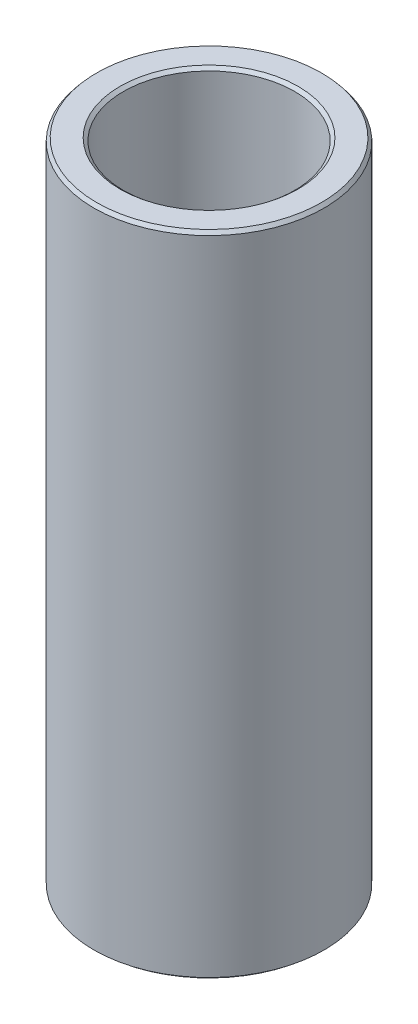
SolidWorks part; units mm, degrees
ref_plane "Front Plane" through (0, 0, 0) normal (0, 0, 1) x (1, 0, 0)
ref_plane "Top Plane" through (0, 0, 0) normal (0, 1, 0) x (1, 0, 0)
ref_plane "Right Plane" through (0, 0, 0) normal (1, 0, 0) x (0, 0, -1)
sketch "Sketch1" plane through (0, 0, 0) normal (0, 1, 0) x (1, 0, 0)
  circle A0 centre (0, 0) radius 30
  dimension "SLEEVE_OD" = 60
extrude "Boss-Extrude1" add sketch "Sketch1" along normal blind 169.0101
sketch "Sketch2" plane through (0, 0, 0) normal (0, 1, 0) x (1, 0, 0)
  circle A0 centre (0, 0) radius 22.3253
  dimension "BORE_D" = 44.6506
extrude "Cut-Extrude1" cut sketch "Sketch2" along normal through all
chamfer "Chamfer1" distance 0.876 angle 39.454 4 edges at (0, 169.0101, 22.3253) (0, 0, 22.3253) (0, 0, 30) (0, 169.0101, 30) first distance on face at (0, 169.0101, 22.3253) first distance on face at (0, 0, 22.3253) first distance on face at (0, 169.0101, 30)
